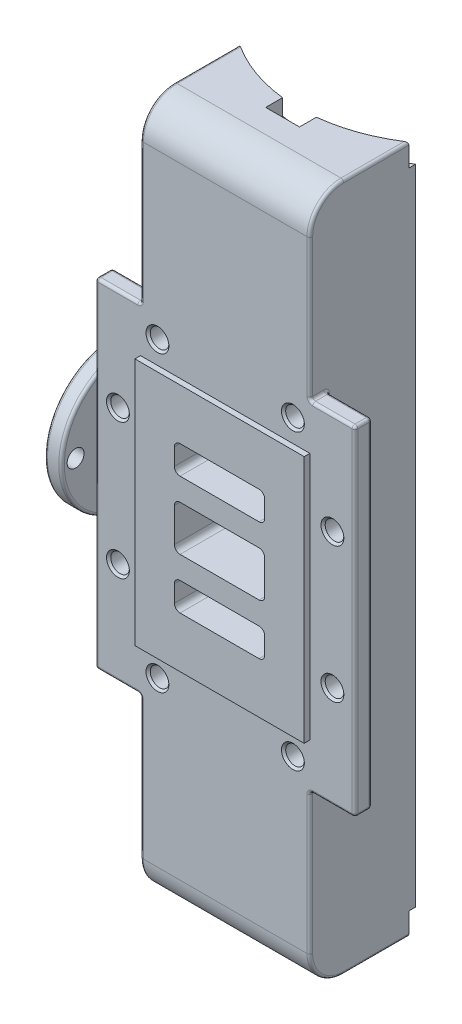
SolidWorks part; units mm, degrees
note: The reader was unsure of these and kept them because the rebuilt part matched: shared geometry of "Sketch1<3>", "Sketch1<6>", "Sketch9<4>", "Sketch9<6>".
ref_plane "Front Plane" through (0, 0, 0) normal (0, 0, 1) x (1, 0, 0)
ref_plane "Top Plane" through (0, 0, 0) normal (0, 1, 0) x (1, 0, 0)
ref_plane "Right Plane" through (0, 0, 0) normal (1, 0, 0) x (0, 0, -1)
sketch "Sketch1" plane through (0, 0, 0) normal (0, 0, 1) x (1, 0, 0)
  line L0 (15, 61) -> (-15, 61)
  line L1 (-15, 61) -> (-15, 30)
  line L2 (-15, 30) -> (-23, 30)
  line L3 (-23, 30) -> (-23, -30)
  line L4 (-23, -30) -> (-15, -30)
  line L5 (-15, -30) -> (-15, -61)
  line L6 (-15, -61) -> (15, -61)
  line L7 (15, -61) -> (15, -30)
  line L8 (15, -30) -> (23, -30)
  line L9 (23, -30) -> (23, 30)
  line L10 (23, 30) -> (15, 30)
  line L11 (15, 30) -> (15, 61)
  line L12 (0, 81.5557) -> (0, -90.9159) construction
  line L13 (-31.9126, 0) -> (38.1925, 0) construction
  line L14 (-15, -22) -> (15, -22)
  line L15 (-15, -22) -> (-15, 22)
  line L16 (-15, 22) -> (15, 22)
  line L17 (15, -22) -> (15, 22)
  line L18 (-15, -22) -> (15, 22) construction
  line L19 (-15, 22) -> (15, -22) construction
  line L20 (-7, 8) -> (7, 8)
  line L21 (-8, 9) -> (-8, 12)
  line L22 (-7, 13) -> (7, 13)
  line L23 (8, 9) -> (8, 12)
  line L24 (-8, 8) -> (8, 13) construction
  line L25 (-8, 13) -> (8, 8) construction
  line L26 (-7, -4) -> (7, -4)
  line L27 (-8, -3) -> (-8, 3)
  line L28 (-7, 4) -> (7, 4)
  line L29 (8, -3) -> (8, 3)
  line L30 (-8, -4) -> (8, 4) construction
  line L31 (-8, 4) -> (8, -4) construction
  line L32 (-7, -13) -> (7, -13)
  line L33 (-8, -12) -> (-8, -9)
  line L34 (-7, -8) -> (7, -8)
  line L35 (8, -12) -> (8, -9)
  line L36 (-8, -13) -> (8, -8) construction
  line L37 (-8, -8) -> (8, -13) construction
  line L38 (-15, 30) -> (-15, -30)
  line L39 (15, 30) -> (15, -30)
  arc A0 (-7, -13) -> (-8, -12) centre (-7, -12) cw
  arc A1 (7, -13) -> (8, -12) centre (7, -12) ccw
  arc A2 (7, -8) -> (8, -9) centre (7, -9) cw
  arc A3 (-8, -9) -> (-7, -8) centre (-7, -9) cw
  arc A4 (7, 4) -> (8, 3) centre (7, 3) cw
  arc A5 (7, -4) -> (8, -3) centre (7, -3) ccw
  arc A6 (-7, -4) -> (-8, -3) centre (-7, -3) cw
  arc A7 (-8, 3) -> (-7, 4) centre (-7, 3) cw
  arc A8 (7, 13) -> (8, 12) centre (7, 12) cw
  arc A9 (7, 8) -> (8, 9) centre (7, 9) ccw
  arc A10 (-7, 8) -> (-8, 9) centre (-7, 9) cw
  arc A11 (-8, 12) -> (-7, 13) centre (-7, 12) cw
  point P17 (23, 0)
  point P18 (0, 0)
  point P19 (0, 61)
  point P24 (0, 10.5)
  point P29 (0, 0)
  point P34 (0, -10.5)
  point P75 (19, 12)
  point P76 (19, -12)
  point P77 (12, 26)
  point P78 (12, -26)
  dimension "D13" = 1
  dimension "D1" = 8
  dimension "D2" = 30
  dimension "D3" = 31
  dimension "D4" = 122
  dimension "D5" = 30
  dimension "D6" = 44
  dimension "D7" = 16
  dimension "D8" = 5
  dimension "D9" = 9
  dimension "D10" = 9
  dimension "D11" = 5
  dimension "D12" = 8
  dimension "D14" = 12
  dimension "D15" = 35
  dimension "D16" = 7
  dimension "D17" = 14
  dimension "D18" = 24
  dimension "D19" = 14
extrude "Boss-Extrude1" add sketch "Sketch1" against normal blind 18.8 contours L39 L11 L0 L1 L38 L16 | L14 L17 L16 L15 L33 A3 L34 A2 L35 A1 L32 A0 L27 A7 L28 A4 L29 A5 L26 A6 L21 A11 L22 A8 L23 A9 L20 A10 | L39 L14 L38 L5 L6 L7
extrude "Boss-Extrude2" add sketch "Sketch1<3>" along normal blind 1 contours L14 L17 L16 L15 L33 A3 L34 A2 L35 A1 L32 A0 L27 A7 L28 A4 L29 A5 L26 A6 L21 A11 L22 A8 L23 A9 L20 A10
sketch "Sketch1<3>" plane through (0, 0, 0) normal (0, 0, 1) x (1, 0, 0) same geometry as "Sketch1"
extrude "Boss-Extrude5" add sketch "Sketch1<6>" against normal blind 3 contours L10 L39 L17 L8 L9 | L38 L2 L3 L4 L15
sketch "Sketch1<6>" plane through (0, 0, 0) normal (0, 0, 1) x (1, 0, 0) same geometry as "Sketch1"
sketch "Sketch4" plane through (0, 0, 0) normal (0, 0, 1) x (1, 0, 0)
  line L0 (15, 61) -> (-15, 61) construction
  point P0 (12, 26)
  point P1 (19, 12)
  point P2 (19, -12)
  point P3 (12, -26)
  dimension "D1" = 12
  dimension "D2" = 35
  dimension "D3" = 7
  dimension "D4" = 14
  dimension "D5" = 24
  dimension "D6" = 14
hole_wizard "M4x0.7 Tapped Hole2" positions "Sketch4" profile "Sketch5" tap size "M4x0.7" standard "ANSI Metric" end condition through all
sketch "Sketch5" plane through (12, 26, 0) normal (1, 0, 0) x (0, -1, 0)
  line L0 (0, 0) -> (0, 18.8)
  line L1 (0, 18.8) -> (1.65, 18.8)
  line L2 (1.65, 18.8) -> (1.65, 0.375)
  line L3 (1.65, 0.375) -> (2.025, 0)
  line L5 (2.025, 0) -> (0, 0)
  line L6 (-1.65, 0.375) -> (-2.025, 0) construction
  line L11 (0, -6.35) -> (0, 107.95) construction
  dimension "Thru Tap Drill Dia." = 3.3
  dimension "Thru Tap Drill Depth" = 18.8
  dimension "Near C'Sink Dia." = 4.05
  dimension "Near C'Sink Angle" = 90
mirror "Mirror2" about plane through (0, 0, 0) normal (1, 0, 0) of "M4x0.7 Tapped Hole2"
fillet "Fillet2" radius 6 2 edges at (0, -61, 0) (0, 61, 0)
sketch "Sketch7" plane through (-15, 0, 0) normal (-1, 0, 0) x (0, 0, 1)
  line L0 (0, -30) -> (0, -55) construction
  circle A0 centre (-10.5, 0) radius 6
  circle A1 centre (-10.5, 0) radius 4.5
  dimension "D2" = 12
  dimension "D3" = 9
  dimension "D1" = 10.5
extrude "Boss-Extrude6" add sketch "Sketch7" along normal blind 12
sketch "Sketch8" plane through (-27, 0, 0) normal (-1, 0, 0) x (0, 0, 1)
  circle A0 centre (-10.5, 0) radius 4.5
  circle A1 centre (-10.5, 0) radius 12.5
  circle A2 centre (-10.5, 0) radius 10 construction
  circle A3 centre (-10.5, 10) radius 1.5
  circle A4 centre (-0.5, 0) radius 1.5
  circle A5 centre (-10.5, -10) radius 1.5
  circle A6 centre (-20.5, 0) radius 1.5
  point P16 (-10.5, 0)
  dimension "D1" = 9
  dimension "D2" = 25
  dimension "D3" = 20
  dimension "D4" = 3
  dimension "D5" = 4
extrude "Boss-Extrude7" add sketch "Sketch8" along normal blind 3
sketch "Sketch9" plane through (0, -61, 0) normal (0, -1, 0) x (1, 0, 0)
  line L0 (-15, -18.8) -> (-15, -6) construction
  line L1 (15, -18.8) -> (15, -6) construction
  line L2 (-15, 0) -> (15, 0) construction
  line L3 (3, -14.1737) -> (3, -10.1737)
  line L4 (3, -10.1737) -> (-3, -10.1737)
  line L5 (-3, -10.1737) -> (-3, -14.1737)
  line L6 (-15, -17.5501) -> (-15, -18.7632)
  line L7 (15, -17.5501) -> (15, -18.7632)
  arc A0 (-15, -18.7632) -> (15, -18.7632) centre (0, -40) cw
  arc A1 (-15, -17.5501) -> (-3, -13.1672) centre (0, -40) cw
  arc A2 (3, -13.1672) -> (15, -17.5501) centre (0, -40) cw
  point P18 (0, -10.1737)
  line M1 (15, -18.8) -> (15, -6)
  line M3 (-15, -6) -> (-15, -18.8)
  dimension "D1" = 26
  dimension "D2" = 27
  dimension "D3" = 40
  dimension "D4" = 3
  dimension "D5" = 4
extrude "Cut-Extrude1" cut sketch "Sketch9" against normal through all
extrude "Cut-Extrude2" cut sketch "Sketch9<4>" against normal blind 4 contours A1 A0 L5 M3 | A2 L3 A0 M1
sketch "Sketch9<4>" plane through (0, -61, 0) normal (0, -1, 0) x (1, 0, 0) same geometry as "Sketch9"
extrude "Cut-Extrude3" cut sketch "Sketch9<6>" against normal blind 48 contours L5 A0 L3 L4
sketch "Sketch9<6>" plane through (0, -61, 0) normal (0, -1, 0) x (1, 0, 0) same geometry as "Sketch9"
mirror "Mirror3" about plane through (0, 0, 0) normal (0, 1, 0) of "Cut-Extrude2", "Cut-Extrude3"
sketch "Sketch11" plane through (-30, 0, 0) normal (-1, 0, 0) x (0, 0, 1)
  circle A1 centre (-10.5, 0) radius 4.5
  dimension "D1" = 9
extrude "Cut-Extrude5" cut sketch "Sketch11" against normal blind 24
fillet "Fillet3" radius 0.5 36 edges at (-15, 61, -11.775) (-15, -61, -11.775) (15, 61, -11.775) (15, -61, -11.775) (-15, 59.2426, -1.7574) (-15, -59.2426, -1.7574) (15, 59.2426, -1.7574) (15, -59.2426, -1.7574) (-15, 42.5, 0) (-15, 0, -3) (-15, -42.5, 0) (15, 42.5, 0) (15, 0, -3) (15, -42.5, 0) (-19, 30, -3) (-15, 30, -1.5) (-19, 30, 0) (-15, -30, -1.5) (-19, -30, -3) (-19, -30, 0) (-23, -30, -1.5) (-23, 0, -3) (-23, 30, -1.5) (-23, 0, 0) (15, 30, -1.5) (19, 30, -3) (19, 30, 0) (23, 30, -1.5) (23, 0, -3) (23, 0, 0) (23, -30, -1.5) (19, -30, -3) (15, -30, -1.5) (19, -30, 0) (-27, -12.5, -10.5) (-30, -12.5, -10.5)
